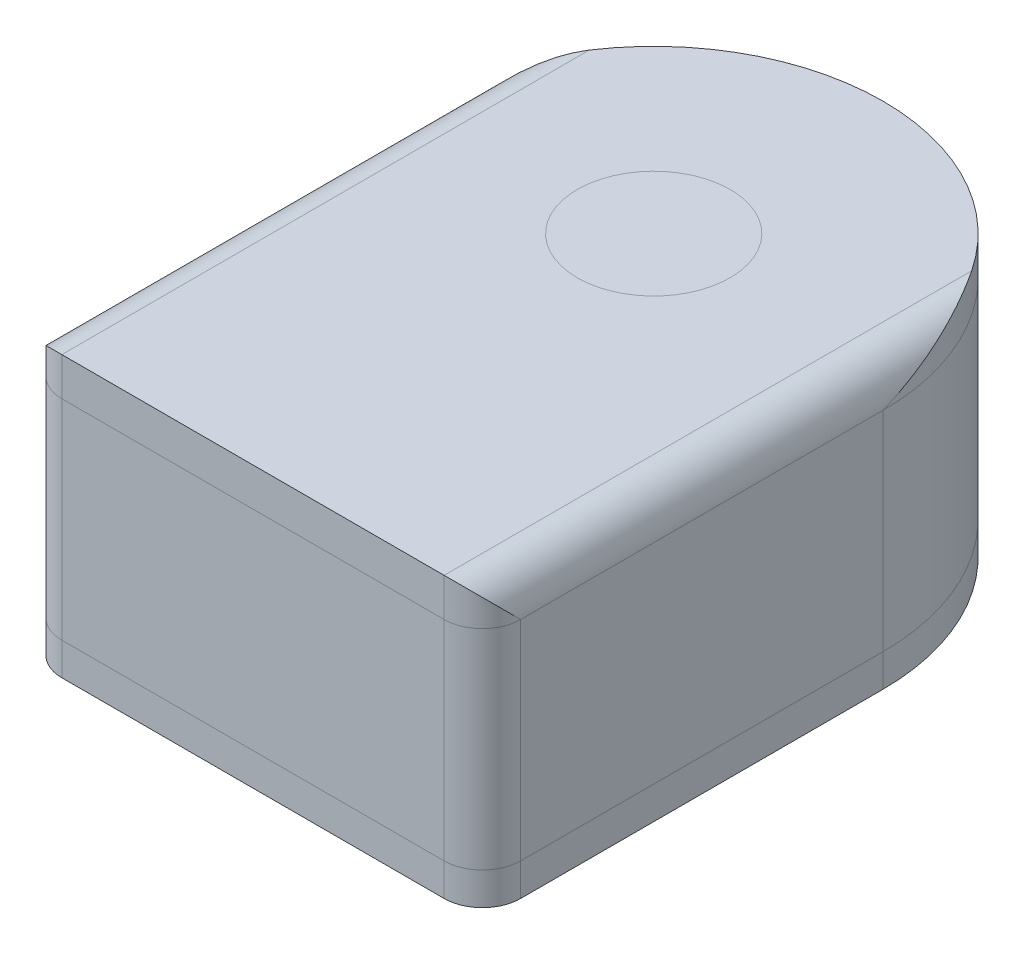
SolidWorks part; units mm, degrees
ref_plane "Plano frontal" through (0, 0, 0) normal (0, 0, 1) x (1, 0, 0)
ref_plane "Plano superior" through (0, 0, 0) normal (0, 1, 0) x (1, 0, 0)
ref_plane "Plano direito" through (0, 0, 0) normal (1, 0, 0) x (0, 0, -1)
sketch "Sketch1" plane through (0, 0, 0) normal (0, 1, 0) x (1, 0, 0)
  line L2 (-15, 13.1) -> (-15, -10.6)
  line L3 (-12.5, -13.1) -> (12.5, -13.1)
  line L4 (15, 13.1) -> (15, -10.6)
  line L5 (-15, 13.1) -> (15, -13.1) construction
  line L6 (-15, -13.1) -> (15, 13.1) construction
  arc A0 (15, 13.1) -> (-15, 13.1) centre (0, 13.1) ccw
  arc A1 (12.5, -13.1) -> (15, -10.6) centre (12.5, -10.6) ccw
  arc A2 (-15, -10.6) -> (-12.5, -13.1) centre (-12.5, -10.6) ccw
  point P0 (0, 0)
  dimension "D2" = 26.2
  dimension "D3" = 2.5
  dimension "D1" = 30
extrude "Boss-Extrude1" add sketch "Sketch1" along normal mid plane 18.3
fillet "Fillet1" radius 2.5 2 edges at (-15, 9.15, -1.25) (15, 9.15, -1.25) tangent propagation no
ref_plane "Plane1" through (0, -7.02, 0) normal (0, -1, 0) x (-1, 0, 0)
split line "Split Line1"
sketch "Sketch3" plane through (0, 9.15, 0) normal (0, 1, 0) x (1, 0, 0)
  circle A0 centre (0, 13.1) radius 5
  dimension "D1" = 10
split line "Split Line2"
sketch "Sketch5" plane through (0, -9.15, 0) normal (0, -1, 0) x (1, 0, 0)
  circle A0 centre (0, -13.1) radius 10.45 construction
  circle A1 centre (0, -13.1) radius 5 construction
  circle A2 centre (0, -23.55) radius 0.8
  circle A3 centre (-9.05, -7.875) radius 0.8
  circle A4 centre (9.05, -7.875) radius 0.8
  point P13 (0, -13.1)
  dimension "D1" = 20.9
  dimension "D2" = 1.6
  dimension "D3" = 3
extrude "Cut-Extrude1" cut sketch "Sketch5" against normal blind 15
sketch "Sketch8" plane through (0, -9.15, 0) normal (0, -1, 0) x (1, 0, 0)
  circle A0 centre (0, -13.1) radius 9.525 construction
  circle A1 centre (-9.525, -13.1) radius 1.25
  circle A2 centre (0, -13.1) radius 5 construction
  circle A3 centre (9.525, -13.1) radius 1.25
  point P10 (0, -13.1)
  dimension "D1" = 19.05
  dimension "D2" = 2.5
  dimension "D3" = 2
extrude "Cut-Extrude2" cut sketch "Sketch8" against normal blind 15
sketch "Sketch9" plane through (0, -9.15, 0) normal (0, -1, 0) x (1, 0, 0)
  circle A0 centre (0, -13.1) radius 5
  circle A1 centre (0, -13.1) radius 5 construction
  dimension "D1" = 10
extrude "Cut-Extrude3" cut sketch "Sketch9" against normal blind 15
sketch "Sketch10" plane through (0, 5.85, 0) normal (0, -1, 0) x (1, 0, 0)
  circle A0 centre (0, -13.1) radius 4
  circle A1 centre (0, -13.1) radius 5
  circle A2 centre (0, -13.1) radius 5
  dimension "D2" = 1
  dimension "D1" = 0
extrude "Boss-Extrude2" add sketch "Sketch10" along normal blind 10
ref_plane "Plane2" through (0, 6.65, 0) normal (0, -1, 0) x (-1, 0, 0)
split line "Split Line3"
